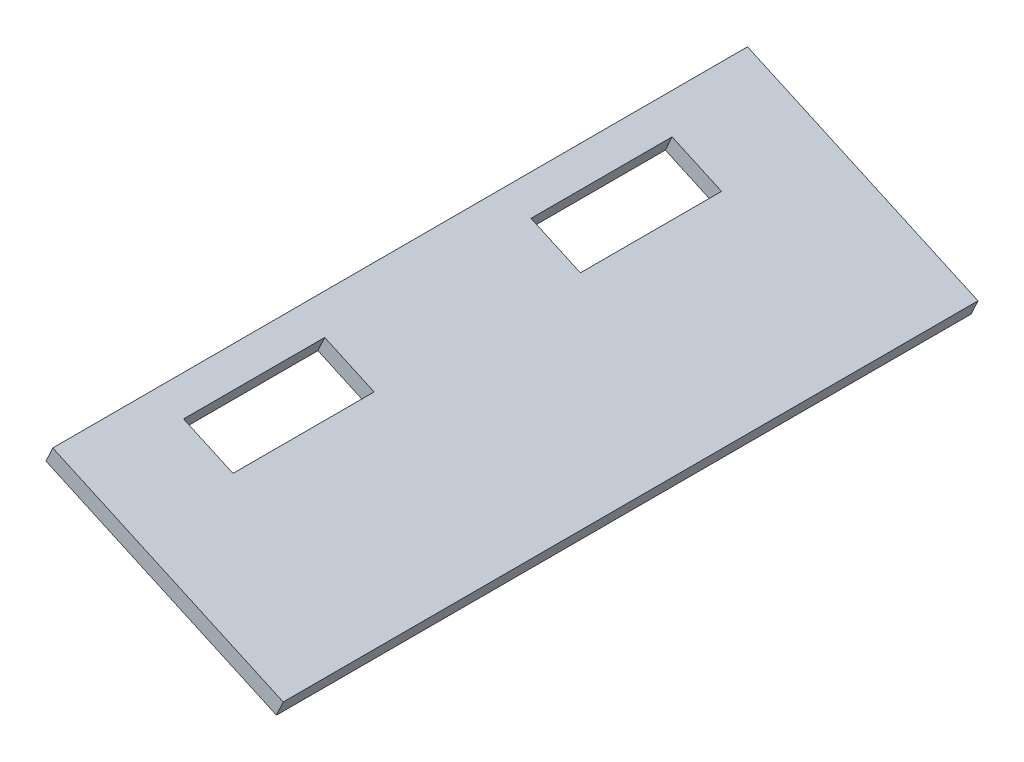
SolidWorks part; units mm, degrees
material "Pine"
ref_plane "Front Plane" through (0, 0, 0) normal (0, 0, 1) x (1, 0, 0)
ref_plane "Top Plane" through (0, 0, 0) normal (0, 1, 0) x (1, 0, 0)
ref_plane "Right Plane" through (0, 0, 0) normal (1, 0, 0) x (0, 0, -1)
sketch "Sketch3" plane through (0, 0, 0) normal (0, 0, 1) x (1, 0, 0)
  line L0 (-108.5345, -3.9032) -> (-108.5345, 1464.0363)
  line L1 (-108.5345, -3.9032) -> (-870.5345, -3.9032)
  line L2 (-870.5345, -3.9032) -> (-870.5345, 625.8363)
  line L3 (-972.1345, 737.9573) -> (-972.1345, 834.2968)
  line L4 (-768.9345, 834.2968) -> (-768.9345, 986.6968)
  line L5 (-972.1345, 834.2968) -> (-768.9345, 834.2968)
  line L6 (-528.0858, 1843.9468) -> (-737.1845, 1843.9468)
  line L7 (-968.4148, 728.977) -> (-874.2542, 634.8165)
  line L8 (-737.1845, 1672.0154) -> (-737.1845, 1762.6932)
  line L9 (-520.195, 1875.6968) -> (-756.2345, 1875.6968)
  line L10 (-112.2542, 1473.0165) -> (-511.2148, 1871.977)
  line L11 (-737.1845, 1692.941) -> (-241.631, 1467.6894)
  line L12 (-596.8655, 1608.234) -> (-737.1845, 983.1768)
  line L13 (-763.9746, 985.3593) -> (-203.7845, 834.2968)
  line L14 (-761.4898, 1669.1128) -> (-638.6318, 1613.2683)
  line L15 (-631.4955, 1598.9249) -> (-768.9345, 986.6968)
  line L16 (-768.9345, 1680.6745) -> (-768.9345, 1862.9968)
  line L17 (-737.1845, 1780.4468) -> (-737.1845, 1843.9468)
  line L18 (-737.1845, 1692.941) -> (-737.1845, 1843.9468) construction
  line L19 (-737.1845, 1692.941) -> (-737.1845, 1762.6932) construction
  line L20 (-838.7845, -3.9032) -> (-838.7845, 834.2968)
  line L21 (-745.0674, 1675.5986) -> (-249.5139, 1450.347) construction
  line L22 (-140.2845, -3.9032) -> (-140.2845, 1456.1455)
  line L23 (-140.2845, 1456.1455) -> (-528.0858, 1843.9468)
  line L24 (-537.8111, 1581.3911) -> (-673.6845, 976.1369)
  line L25 (-768.9345, 966.9663) -> (-203.7845, 814.5663)
  line L26 (-737.1845, 1672.0154) -> (-203.7845, 1429.5608)
  line L27 (-528.0858, 1843.9468) -> (-554.3883, 1780.4468)
  line L28 (-140.2845, 1456.1455) -> (-203.7845, 1429.8429)
  line L29 (-775.2845, -3.9032) -> (-775.2845, 834.2968)
  line L30 (-773.8944, 968.3038) -> (-208.7444, 815.9038) construction
  line L31 (-203.7845, -3.9032) -> (-203.7845, 1429.8429)
  line L32 (-203.7845, 1429.8429) -> (-554.3883, 1780.4468)
  line L33 (-554.3883, 1780.4468) -> (-737.1845, 1780.4468)
  line L34 (-768.9345, 966.9663) -> (-763.9746, 985.3593)
  line L35 (-737.1845, 1762.6932) -> (-369.5099, 1595.5683)
  line L36 (-673.6845, 1733.8295) -> (-599.2171, 1699.9807) construction
  line L37 (-737.1845, 1692.941) -> (-625.4936, 1642.1724) construction
  line L38 (-538.5586, 1578.0615) -> (-673.6845, 976.1369) construction
  line L39 (-600.5166, 1591.9704) -> (-737.1845, 983.1768) construction
  line L40 (-554.3883, 1780.4468) -> (-673.6845, 1780.4468) construction
  line L41 (-203.7845, 91.3468) -> (-203.7845, 1429.8429) construction
  line L42 (-140.2845, 27.8468) -> (-140.2845, 1456.1455) construction
  line L43 (-775.2845, 91.3468) -> (-775.2845, 625.8363) construction
  line L44 (-838.7845, 27.8468) -> (-838.7845, 625.8363) construction
  line L45 (-203.7845, 91.3468) -> (-775.2845, 91.3468) construction
  line L46 (-140.2845, 27.8468) -> (-838.7845, 27.8468) construction
  line L47 (-940.3845, 745.8481) -> (-851.8036, 657.2672) construction
  line L48 (-843.7807, 739.0468) -> (-806.9023, 702.1685) construction
  line L49 (-843.7807, 739.0468) -> (-673.6845, 739.0468) construction
  line L50 (-940.3845, 802.5468) -> (-737.1845, 802.5468) construction
  line L51 (-940.3845, 745.8481) -> (-940.3845, 802.5468) construction
  line L52 (-843.7807, 739.0468) -> (-843.7807, 739.0468) construction
  line L53 (-673.6845, 1733.8295) -> (-673.6845, 1780.4468) construction
  line L54 (-756.2345, 1692.941) -> (-756.2345, 1792.2779) construction
  line L55 (-756.2345, 1792.2779) -> (-361.627, 1612.9108) construction
  line L56 (-673.6845, 739.0468) -> (-673.6845, 976.1369) construction
  line L57 (-737.1845, 802.5468) -> (-737.1845, 983.1768) construction
  line L58 (-768.9345, 986.6968) -> (-203.7845, 834.2968) construction
  line L59 (-203.7845, 834.2968) -> (-208.7444, 815.9038)
  line L60 (-768.9345, 901.198) -> (-203.7845, 748.798)
  line L61 (-846.7775, 922.1894) -> (-163.9675, 738.0608) construction
  line L62 (-768.9345, 966.9663) -> (-208.7444, 815.9038) construction
  line L64 (-808.7515, 1063.2022) -> (-125.9415, 879.0737) construction
  line L65 (-125.9415, 879.0737) -> (-163.9675, 738.0608) construction
  line L66 (-846.7775, 922.1894) -> (-808.7515, 1063.2022) construction
  arc A0 (-108.5345, 1464.0363) -> (-112.2542, 1473.0165) centre (-121.2345, 1464.0363) ccw
  arc A1 (-511.2148, 1871.977) -> (-520.195, 1875.6968) centre (-520.195, 1862.9968) ccw
  arc A2 (-768.9345, 1862.9968) -> (-756.2345, 1875.6968) centre (-756.2345, 1862.9968) cw
  arc A3 (-768.9345, 1680.6745) -> (-761.4898, 1669.1128) centre (-756.2345, 1680.6745) ccw
  arc A4 (-631.4955, 1598.9249) -> (-638.6318, 1613.2683) centre (-643.8871, 1601.7067) ccw
  arc A5 (-972.1345, 737.9573) -> (-968.4148, 728.977) centre (-959.4345, 737.9573) ccw
  arc A6 (-870.5345, 625.8363) -> (-874.2542, 634.8165) centre (-883.2345, 625.8363) ccw
  arc A7 (-737.1845, 1843.9468) -> (-737.1845, 1843.9468) centre (-737.1845, 1843.9468) cw
  arc A8 (-737.1845, 1692.941) -> (-737.1845, 1692.941) centre (-737.1845, 1692.941) ccw
  arc A12 (-140.2845, 1456.1455) -> (-140.2845, 1456.1455) centre (-140.2845, 1456.1455) ccw
  arc A13 (-528.0858, 1843.9468) -> (-528.0858, 1843.9468) centre (-528.0858, 1843.9468) ccw
  arc A14 (-600.5166, 1591.9704) -> (-625.4936, 1642.1724) centre (-643.8871, 1601.7067) ccw construction
  arc A16 (-203.7845, 1429.8429) -> (-203.7845, 1429.8429) centre (-203.7845, 1429.8429) ccw
  arc A17 (-554.3883, 1780.4468) -> (-554.3883, 1780.4468) centre (-554.3883, 1780.4468) ccw
  arc A18 (-673.6845, 1780.4468) -> (-673.6845, 1780.4468) centre (-673.6845, 1780.4468) cw
  arc A19 (-673.6845, 1733.8295) -> (-673.6845, 1733.8295) centre (-673.6845, 1733.8295) ccw
  arc A20 (-838.7845, 625.8363) -> (-851.8036, 657.2672) centre (-883.2345, 625.8363) ccw construction
  arc A21 (-775.2845, 625.8363) -> (-806.9023, 702.1685) centre (-883.2345, 625.8363) ccw construction
  arc A22 (-843.7807, 739.0468) -> (-843.7807, 739.0468) centre (-843.7807, 739.0468) ccw construction
  arc A23 (-940.3845, 745.8481) -> (-940.3845, 745.8481) centre (-940.3845, 745.8481) ccw construction
  arc A24 (-756.2345, 1692.941) -> (-745.0674, 1675.5986) centre (-737.1845, 1692.941) ccw construction
  dimension "D1" = 12.7
  dimension "D2" = 31.75
  dimension "D3" = 63.5
  dimension "D4" = 19.05
  dimension "D5" = 19.05
  dimension "D6" = 63.5
sketch "Sketch6" plane through (0, 0, 0) normal (0, 0, 1) x (1, 0, 0)
  line L1 (-729.3016, 1689.3579) -> (-459.7048, 1566.8139)
  line L2 (-737.1845, 1672.0154) -> (-467.5877, 1549.4714)
  line L3 (-737.1845, 1672.0154) -> (-729.3016, 1689.3579)
  line L5 (-459.7048, 1566.8139) -> (-467.5877, 1549.4714)
extrude "Boss-Extrude1" add sketch "Sketch6" along normal blind 812.8
sketch "Sketch8" plane through (503.6386, 1108.0049, 0) normal (-0.4138, -0.9104, 0) x (0.9104, -0.4138, 0)
  line L0 (-1263.906, 120.65) -> (-1263.906, 285.75)
  line L1 (-1263.906, 285.75) -> (-1327.406, 285.75)
  line L2 (-1327.406, 285.75) -> (-1327.406, 120.65)
  line L3 (-1327.406, 120.65) -> (-1263.906, 120.65)
  line L4 (-1327.406, 692.15) -> (-1263.906, 692.15)
  line L5 (-1327.406, 527.05) -> (-1327.406, 692.15)
  line L6 (-1263.906, 527.05) -> (-1327.406, 527.05)
  line L7 (-1263.906, 692.15) -> (-1263.906, 527.05)
extrude "Cut-Extrude1" cut sketch "Sketch8" against normal blind 19.05
